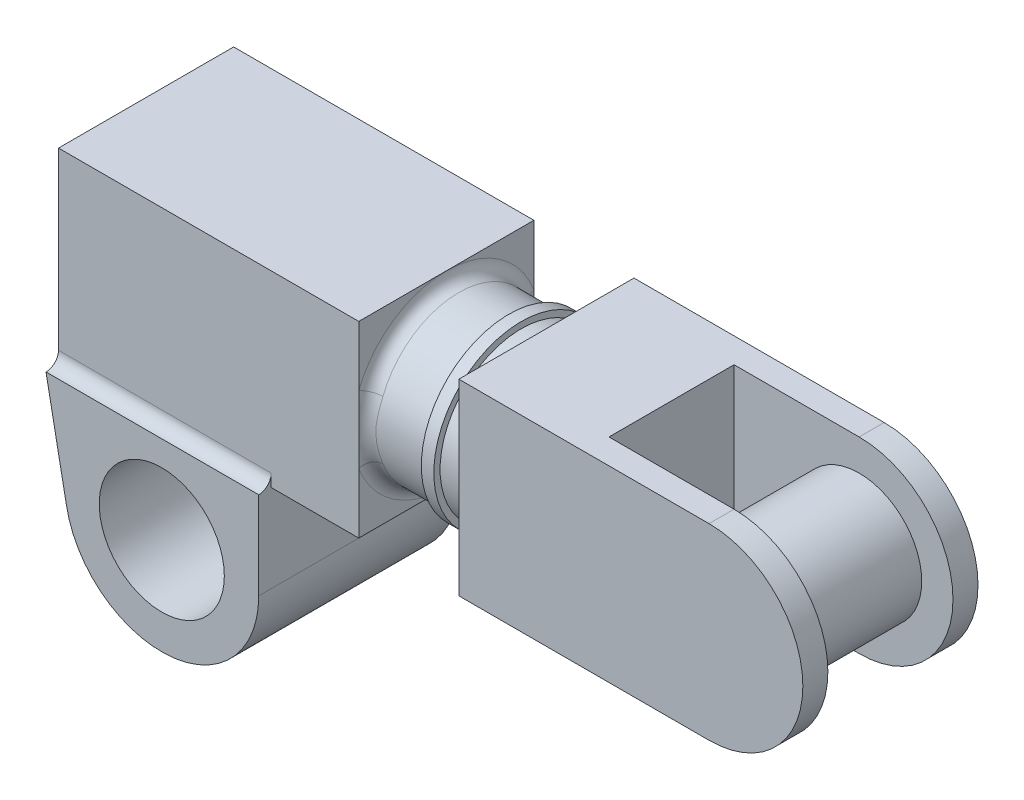
SolidWorks part; units mm, degrees
ref_plane "Front Plane" through (0, 0, 0) normal (0, 0, 1) x (1, 0, 0)
ref_plane "Top Plane" through (0, 0, 0) normal (0, 1, 0) x (1, 0, 0)
ref_plane "Right Plane" through (0, 0, 0) normal (1, 0, 0) x (0, 0, -1)
sketch "Sketch1" plane through (0, 0, 0) normal (1, 0, 0) x (0, 0, -1)
  line L1 (-70, 75) -> (70, 75)
  line L2 (-70, 75) -> (-70, -75)
  line L3 (-70, -75) -> (70, -75)
  line L4 (70, 75) -> (70, -75)
  line L5 (-70, 75) -> (70, -75) construction
  line L6 (-70, -75) -> (70, 75) construction
  point P0 (0, 0)
  dimension "D1" = 150
  dimension "D2" = 140
extrude "Boss-Extrude1" add sketch "Sketch1" along normal blind 240
sketch "Sketch2" plane through (240, 0, 0) normal (1, 0, 0) x (0, 0, -1)
  circle A0 centre (0, 0) radius 65
  dimension "D1" = 130
extrude "Boss-Extrude2" add sketch "Sketch2" along normal blind 50
sketch "Sketch3" plane through (290, 0, 0) normal (1, 0, 0) x (0, 0, -1)
  circle A0 centre (0, 0) radius 70
  dimension "D1" = 140
extrude "Boss-Extrude3" add sketch "Sketch3" along normal blind 10
sketch "Sketch4" plane through (0, 0, 0) normal (0, 0, 1) x (1, 0, 0)
  line L0 (0, -75) -> (16.2188, -158.4383)
  line L1 (0, 75) -> (0, -75) construction
  line L2 (170.0448, -145) -> (170.0448, -75)
  line L3 (240, -75) -> (0, -75) construction
  line L4 (0, -75) -> (170.0448, -75)
  circle A0 centre (92.5448, -145) radius 50
  arc A1 (16.2188, -158.4383) -> (170.0448, -145) centre (92.5448, -145) ccw
  dimension "D1" = 155
  dimension "D2" = 100
  dimension "D3" = 191
  dimension "D4" = 85
  dimension "D5" = 70
  dimension "D6" = 70
extrude "Boss-Extrude4" add sketch "Sketch4" along normal mid plane 160
fillet "Fillet1" radius 10 3 edges at (85.0224, -75, -70) (85.0224, -75, 70) (240, 0, -65)
sketch "Sketch6" plane through (300, 0, 0) normal (1, 0, 0) x (0, 0, -1)
  circle A0 centre (0, 0) radius 65
  dimension "D1" = 130
extrude "Boss-Extrude5" add sketch "Sketch6" along normal blind 20
sketch "Sketch7" plane through (0, 0, 0) normal (0, 0, 1) x (1, 0, 0)
  line L0 (520, 75) -> (320, 75)
  line L1 (320, 75) -> (320, -75)
  line L2 (320, -75) -> (520, -75)
  line L4 (320, -65) -> (320, 65) construction
  arc A0 (520, -75) -> (520, 75) centre (520, 0) ccw
  dimension "D1" = 150
  dimension "D2" = 200
extrude "Boss-Extrude6" add sketch "Sketch7" along normal mid plane 140
sketch "Sketch8" plane through (0, 0, 0) normal (0, 0, 1) x (1, 0, 0)
  line L0 (520, 75) -> (420, 75)
  line L1 (520, 75) -> (320, 75) construction
  line L2 (420, 75) -> (420, -75)
  line L3 (320, -75) -> (520, -75) construction
  line L4 (420, -75) -> (520, -75)
  arc A0 (520, -75) -> (520, 75) centre (520, 0) ccw construction
  arc A1 (520, -75) -> (520, 75) centre (520, 0) ccw
extrude "Cut-Extrude1" cut sketch "Sketch8" against normal mid plane 100
sketch "Sketch9" plane through (0, 0, -50) normal (0, 0, 1) x (1, 0, 0)
  circle A0 centre (520, 0) radius 50
  dimension "D1" = 100
extrude "Boss-Extrude7" add sketch "Sketch9" along normal blind 100
